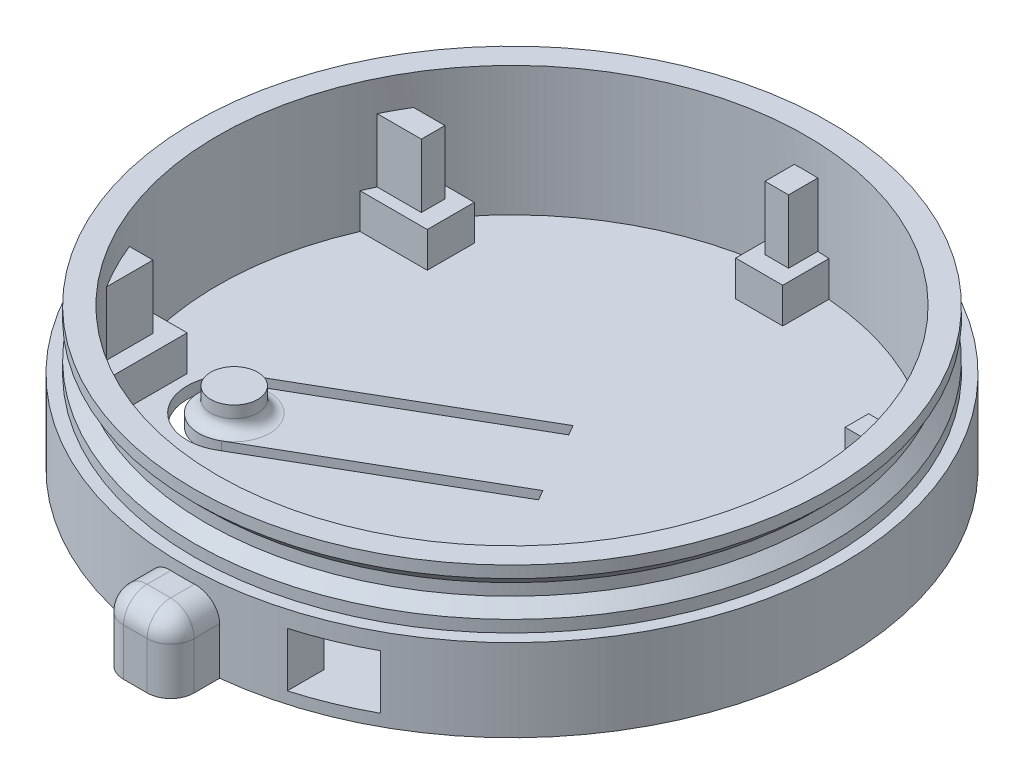
SolidWorks part; units mm, degrees
note: The reader was unsure of these and kept them because the rebuilt part matched: shared geometry of "Sketch1<2>", "Sketch1<3>".
ref_plane "Front Plane" through (0, 0, 0) normal (0, 0, 1) x (1, 0, 0)
ref_plane "Top Plane" through (0, 0, 0) normal (0, 1, 0) x (1, 0, 0)
ref_plane "Right Plane" through (0, 0, 0) normal (1, 0, 0) x (0, 0, -1)
sketch "Sketch1" plane through (0, 0, 0) normal (0, 1, 0) x (1, 0, 0)
  circle A0 centre (0, 0) radius 13.5
  circle A1 centre (0, 0) radius 12.5
  point P3 (0, 0)
extrude "Boss-Extrude1" add sketch "Sketch1" along normal blind 6
extrude "Boss-Extrude3" add sketch "Sketch1<2>" along normal blind 0.5 contours A1
sketch "Sketch1<2>" plane through (0, 0, 0) normal (0, 1, 0) x (1, 0, 0) same geometry as "Sketch1"
extrude "Extrude-Thin1" add sketch "Sketch1<3>" along normal blind 3.5 thin contours A0
sketch "Sketch1<3>" plane through (0, 0, 0) normal (0, 1, 0) x (1, 0, 0) same geometry as "Sketch1"
sketch "Sketch12" plane through (0, 0.5, 0) normal (0, 1, 0) x (1, 0, 0)
  line L0 (0, 0) -> (0, 10.5) construction
  line L1 (1, 10.5) -> (-1, 10.5)
  line L2 (-1, 10.5) -> (-1, 12.4599)
  line L3 (1, 10.5) -> (1, 12.4599)
  line L4 (0, 0) -> (-8.6, 0) construction
  line L5 (-8.6, 0) -> (-8.6, 5) construction
  line L6 (-8.6, 5) -> (-11.4564, 5)
  line L7 (-11.4564, 5) -> (-8.6, 5)
  line L8 (-8.6, 5) -> (-8.6, 7)
  line L9 (-8.6, 7) -> (-10.3562, 7)
  line L10 (0, 0) -> (9.5, 0) construction
  line L11 (9.5, 0) -> (9.5, 3.4) construction
  line L12 (9.5, 3.4) -> (12.0287, 3.4)
  line L13 (9.5, 3.4) -> (9.5, 5.4)
  line L14 (9.5, 5.4) -> (11.2734, 5.4)
  line L15 (0, 0) -> (0, -3.9) construction
  line L16 (0, -3.9) -> (-9.9, -3.9) construction
  line L17 (-9.9, -3.9) -> (-11.876, -3.9)
  line L18 (-9.9, -3.9) -> (-9.9, -7.6315)
  line L19 (9.5, 0) -> (9.5, -4.1) construction
  line L20 (-8.6, 7) -> (-8.6, 9.0714)
  line L21 (8.25, -2.85) -> (10.75, -2.85)
  line L22 (8.25, -2.85) -> (8.25, -5.35)
  line L23 (8.25, -5.35) -> (10.75, -5.35)
  line L24 (10.75, -2.85) -> (10.75, -5.35)
  line L25 (8.25, -2.85) -> (10.75, -5.35) construction
  line L26 (8.25, -5.35) -> (10.75, -2.85) construction
  line L27 (-1, 10.5) -> (-6.7823, 10.5)
  line L28 (9.5, 5.4) -> (9.5, 8.124)
  line L29 (1, 10.5) -> (6.7823, 10.5)
  circle A0 centre (0, 0) radius 12.5 construction
  circle A1 centre (0, 0) radius 12.5 construction
  circle A2 centre (9.5, -4.1) radius 0.5
  point P5 (1, 10.5)
  circle M13 centre (0, 0) radius 12.5
extrude "Boss-Extrude10" add sketch "Sketch12" along normal blind 1.5 contours L8 L9 L6 M13 | L1 L3 L2 M13 | L14 L13 L12 M13 | L18 L17 M13 | L24 L21 L22 L23 A2
sketch "Sketch15" plane through (0, 2, 0) normal (0, 1, 0) x (1, 0, 0)
  line L0 (-8.6, 6) -> (-9.35, 6)
  line L1 (-0.5, 11.25) -> (-0.5, 12.49)
  line L2 (-8.6, 5) -> (-8.6, 7) construction
  line L3 (-9.35, 6) -> (-9.35, 6.5)
  line L4 (-9.35, 6) -> (-9.35, 5.5)
  line L5 (-9.35, 5.5) -> (-11.225, 5.5)
  line L6 (-9.35, 6.5) -> (-10.6771, 6.5)
  line L7 (0, 10.5) -> (0, 11.25)
  line L8 (1, 10.5) -> (-1, 10.5) construction
  line L9 (-0.5, 11.25) -> (0.5, 11.25)
  line L10 (0.5, 11.25) -> (0.5, 12.49)
  line L11 (9.5, 4.4) -> (10.25, 4.4)
  line L12 (9.5, 3.4) -> (9.5, 5.4) construction
  line L13 (10.25, 4.9) -> (10.25, 3.9)
  line L14 (10.25, 4.9) -> (11.4996, 4.9)
  line L15 (10.25, 3.9) -> (11.876, 3.9)
  line L16 (-10.6029, -4.65) -> (-10.6029, -6.6203)
  line L18 (-11.6029, -4.65) -> (-10.6029, -4.65)
  arc A0 (1, 12.4599) -> (-1, 12.4599) centre (0, 0) ccw construction
  arc A1 (-10.3562, 7) -> (-11.4564, 5) centre (0, 0) ccw construction
  arc A2 (12.0287, 3.4) -> (11.2734, 5.4) centre (0, 0) ccw construction
  circle A3 centre (0, 0) radius 12.5 construction
  arc A5 (-11.876, -3.9) -> (-9.9, -7.6315) centre (0, 0) ccw construction
  arc A6 (-10.6771, 6.5) -> (-11.225, 5.5) centre (0, 0) ccw
  arc A7 (-11.6029, -4.65) -> (-10.6029, -6.6203) centre (0, 0) ccw
  arc A8 (11.876, 3.9) -> (11.4996, 4.9) centre (0, 0) ccw
  arc A9 (0.5, 12.49) -> (-0.5, 12.49) centre (0, 0) ccw
  point P19 (0, 11.25)
  point P31 (10.25, 4.4)
  arc M12 (-10.3562, 7) -> (-11.4564, 5) centre (0, 0) ccw
extrude "Boss-Extrude12" add sketch "Sketch15" along normal blind 2.7 contours L10 A9 L1 L9 | L3 L6 L5 L4 M12 | L18 A7 L16 | L15 A8 L14 L13
sketch "Sketch13" plane through (0, 0.5, 0) normal (0, 1, 0) x (1, 0, 0)
  line L0 (-6.4498, -6.082) -> (-8.4502, -2.618)
  line L1 (-8.4502, -2.618) -> (0.2096, 2.3828)
  line L2 (0, 0) -> (-7.45, -4.35)
  line L3 (-8.2001, -3.051) -> (0.4596, 1.9498)
  line L4 (-6.4498, -6.082) -> (2.2099, -1.0811)
  line L5 (-6.6999, -5.649) -> (1.9599, -0.6481)
  line L6 (0.2096, 2.3828) -> (0.4596, 1.9498)
  line L7 (1.9599, -0.6481) -> (2.2099, -1.0811)
  circle A0 centre (-7.45, -4.35) radius 2
  circle A1 centre (-7.45, -4.35) radius 1.5
  point P7 (-7.45, -4.35)
extrude "Cut-Extrude1" cut sketch "Sketch13" against normal blind 10 contours A0 L3 L6 L1 | L3 A0 L0 | A1 L0 A0 | L0 A0 L5 | A0 L4 L7 L5
sketch "Sketch14" plane through (0, 0.5, 0) normal (0, 1, 0) x (1, 0, 0)
  circle A0 centre (-7.45, -4.35) radius 1
extrude "Boss-Extrude11" add sketch "Sketch14" along normal blind 1 contours A0
fillet "Fillet7" radius 0.5 1 edges at (-7.45, 0.5, 5.35)
sketch "Sketch16" plane through (0, 0.5, 0) normal (0, 1, 0) x (1, 0, 0)
  line L3 (3.9, -10.1) -> (3.9, -13.4458)
  line L4 (6.7, -9.45) -> (6.7, -12.2927)
  line L5 (6.7, -9.45) -> (3.9, -10.1)
  arc A7 (3.9, -13.4458) -> (6.7, -12.2927) centre (0, 0) ccw
extrude "Cut-Extrude2" cut sketch "Sketch16" along normal blind 2.3
sketch "Sketch17" plane through (0, 0, 0) normal (0, -1, 0) x (-1, 0, 0)
  line L1 (0.5, 16) -> (-0.5, 16)
  line L2 (1.5, 15) -> (1.5, -15)
  line L3 (0.5, -16) -> (-0.5, -16)
  line L4 (-1.5, 15) -> (-1.5, -15)
  line L5 (1.5, 16) -> (-1.5, -16) construction
  line L6 (1.5, -16) -> (-1.5, 16) construction
  arc A0 (-0.5, -16) -> (-1.5, -15) centre (-0.5, -15) cw
  arc A1 (1.5, -15) -> (0.5, -16) centre (0.5, -15) cw
  arc A2 (-0.5, 16) -> (-1.5, 15) centre (-0.5, 15) ccw
  arc A3 (0.5, 16) -> (1.5, 15) centre (0.5, 15) cw
  circle A4 centre (0, 0) radius 14
  point P0 (0, 0)
  circle M5 centre (0, 0) radius 14
  dimension "D1" = 1
extrude "Boss-Extrude13" add sketch "Sketch17" against normal blind 3 separate body contours A1 L2 L4 A0 L3 M5 | A3 L1 A2 L4 L2 M5
fillet "Fillet8" radius 1 5 edges at (-1.5, 3, -14.4597) (-1.2071, 3, -15.7071) (1.5, 3, -14.4597) (1.2071, 3, -15.7071) (0, 3, -16)
fillet "Fillet9" radius 1 5 edges at (-1.5, 3, 14.4597) (-1.2071, 3, 15.7071) (1.5, 3, 14.4597) (1.2071, 3, 15.7071) (0, 3, 16)
sketch "Sketch18" plane through (0, 3.5, 0) normal (0, 1, 0) x (1, 0, 0)
  circle A1 centre (0, 0) radius 13
  circle A2 centre (0, 0) radius 13.5
extrude "Cut-Extrude3" cut sketch "Sketch18" along normal blind 0.5 from offset 1
chamfer "Chamfer1" distance 0.5 angle 45 1 edges at (0, 5, 13.5)
sketch "Sketch7" plane through (0, 0, 0) normal (0, 1, 0) x (1, 0, 0)
  circle A1 centre (40, 0) radius 14.5
extrude "Boss-Extrude2" [suppressed] add sketch "Sketch7" along normal blind 0.5 separate body
sketch "Sketch19" [suppressed] plane through (0, 0, 0) normal (0, -1, 0) x (-1, 0, 0)
  circle A0 centre (-40, 0) radius 14.5
  circle A1 centre (-40, 0) radius 13.5
extrude "Boss-Extrude14" [suppressed] add sketch "Sketch19" along normal blind 6.5
sketch "Sketch20" [suppressed] plane through (0, -6.5, 0) normal (0, -1, 0) x (-1, 0, 0)
  circle A0 centre (-40, 0) radius 13.5
  circle A1 centre (-40, 0) radius 13
extrude "Boss-Extrude15" [suppressed] add sketch "Sketch20" against normal blind 0.5
sketch "Sketch21" [suppressed] plane through (0, 0.5, 0) normal (0, -1, 0) x (-1, 0, 0)
  line L1 (-56.75, 8.5) -> (-23.25, 8.5)
  line L2 (-56.75, 8.5) -> (-56.75, -8.5)
  line L3 (-56.75, -8.5) -> (-23.25, -8.5)
  line L4 (-23.25, 8.5) -> (-23.25, -8.5)
  line L5 (-56.75, 8.5) -> (-23.25, -8.5) construction
  line L6 (-56.75, -8.5) -> (-23.25, 8.5) construction
  line L7 (-58.5, 10) -> (-21.5, 10)
  line L8 (-58.5, 10) -> (-58.5, -10)
  line L9 (-58.5, -10) -> (-21.5, -10)
  line L10 (-21.5, 10) -> (-21.5, -10)
  line L11 (-58.5, 10) -> (-21.5, -10) construction
  line L12 (-58.5, -10) -> (-21.5, 10) construction
  circle A0 centre (-40, 0) radius 14.5
  point P0 (-40, 0)
  point P6 (-40, 0)
  circle M18 centre (-40, 0) radius 14.5
extrude "Boss-Extrude16" [suppressed] add sketch "Sketch21" along normal blind 3 contours L9 L8 L7 L1 L2 L3 M18 | L7 L10 L9 L3 L4 L1 M18
fillet "Fillet10" [suppressed] radius 10
fillet "Fillet11" [suppressed] radius 2
fillet "Fillet12" [suppressed] radius 0.5
sketch "Sketch22" [suppressed] plane through (0, 0, 0) normal (0, -1, 0) x (-1, 0, 0)
  line L0 (-29.3, -1.45) -> (-29.3, -2.05) construction
  line L1 (-28.55, -1.45) -> (-28.55, -2.05)
  line L2 (-30.05, -1.45) -> (-30.05, -2.05)
  arc A0 (-28.55, -1.45) -> (-30.05, -1.45) centre (-29.3, -1.45) ccw
  arc A1 (-30.05, -2.05) -> (-28.55, -2.05) centre (-29.3, -2.05) ccw
  point P2 (-29.3, -1.75)
extrude "Cut-Extrude4" [suppressed] cut sketch "Sketch22" against normal through all
chamfer "Chamfer2" [suppressed] distance 0.2 distance2 0.5
sketch "Sketch24" [suppressed] plane through (0, 0, 0) normal (0, -1, 0) x (-1, 0, 0)
  circle A1 centre (-40, -4) radius 8
  arc A2 (-34.6404, -11.8437) -> (-45.3596, -11.8437) centre (-40, -4) ccw
  arc A3 (-45.3596, -11.8437) -> (-34.6404, -11.8437) centre (-40, 0) ccw
extrude "Boss-Extrude23" [suppressed] add sketch "Sketch24" along normal blind 3
sketch "Sketch23" [suppressed] plane through (0, 0, 0) normal (0, -1, 0) x (-1, 0, 0)
  circle A0 centre (-40, -4) radius 8
extrude "Cut-Extrude5" [suppressed] cut sketch "Sketch23" against normal through all
thread "Thread1" [suppressed] pitch 1.5 start angle 0, offset 0, length 0, pitch 1.5, diameter 16
ref_plane "Plane2" through (48, -3, 4) normal (0, 0, 1) x (1, 0, 0)
sketch "Thread Profile2" plane through (48, -3, 4) normal (0, 0, 1) x (1, 0, 0)
  line L0 (0, 0) -> (0, 1.5) construction
  line L1 (0, 0) -> (0.8119, 0.4687)
  line L2 (0.8119, 0.4687) -> (0.8119, 0.6562)
  line L3 (0.8119, 0.6562) -> (0, 1.125)
  line L4 (0.8119, 0.5625) -> (0, 0.5625) construction
  line L11 (0, 0) -> (0, 1.125)
  point P2 (0, 0)
  dimension "Pitch" = 1.5
  dimension "Profile_Angle" = 60
  dimension "Profile_Land" = 0.1875
  dimension "Profile_Height" = 0.8119
chamfer "Chamfer3" distance 0.5 angle 45 1 edges at (0, 4.5, 13.5)
